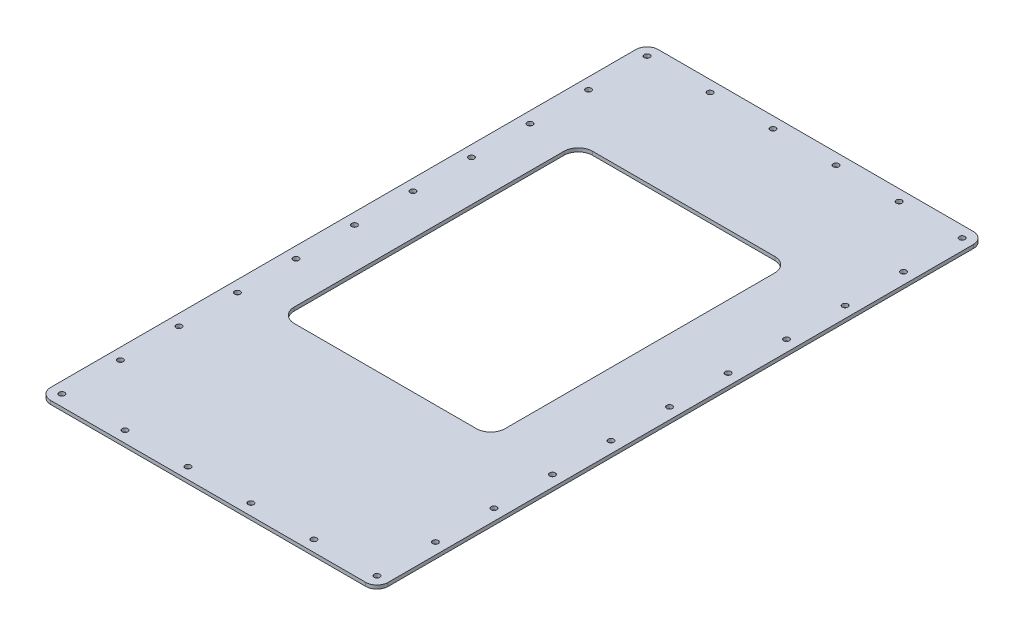
SolidWorks part; units mm, degrees
material "5052-H32"
ref_plane "Front Plane" through (0, 0, 0) normal (0, 0, 1) x (1, 0, 0)
ref_plane "Top Plane" through (0, 0, 0) normal (0, 1, 0) x (1, 0, 0)
ref_plane "Right Plane" through (0, 0, 0) normal (1, 0, 0) x (0, 0, -1)
sketch "Sketch9" plane through (0, 0, 0) normal (0, 1, 0) x (1, 0, 0)
  line L0 (-130, 0) -> (130, 0) construction
  line L1 (-130, 500) -> (130, 500) construction
  line L2 (-130, 500) -> (-130, 0) construction
  line L4 (130, 500) -> (130, 0) construction
  line L14 (83.6625, 147.4437) -> (-103.6625, 147.4437)
  line L15 (-150, 520) -> (150, 520)
  line L16 (150, 520) -> (150, -20)
  line L17 (-150, -20) -> (150, -20)
  line L18 (-150, 520) -> (-150, -20)
  line L19 (-10, 280) -> (155.5075, 280) construction
  line L20 (83.6625, 147.4437) -> (83.6625, 412.5562)
  line L21 (83.6625, 412.5562) -> (-103.6625, 412.5562)
  line L22 (-103.6625, 147.4437) -> (-103.6625, 412.5562)
  line L23 (83.6625, 147.4437) -> (-103.6625, 412.5562) construction
  line L24 (83.6625, 412.5562) -> (-103.6625, 147.4437) construction
  line L25 (-130, 0) -> (130, 0) construction
  point P5 (-10, 280)
  point P19 (0, 0)
  dimension "D10" = 500
  dimension "D9" = 260
  dimension "D3" = 265.1125
  dimension "D4" = 187.325
  dimension "D5" = 220
  dimension "D6" = 140
  dimension "D2" = 20
extrude "Boss-Extrude7" add sketch "Sketch9" along normal blind 3.175 separate body contours L15 L18 L17 L16 region at (0, 0, -513.8226)
fillet "Fillet4" radius 10 4 edges at (-150, 1.5875, -520) (150, 1.5875, -520) (-150, 1.5875, 20) (150, 1.5875, 20)
sketch "Sketch10" plane through (0, 0, 0) normal (0, 1, 0) x (1, 0, 0)
  line L0 (0, 0) -> (0, 500) construction
  line L1 (-130, 500) -> (130, 500) construction
  line L2 (-130, 500) -> (-130, 0) construction
  line L3 (-130, 0) -> (130, 0) construction
  line L4 (130, 500) -> (130, 0) construction
  line L8 (-150, 520) -> (-150, -20) construction
  line L9 (-150, -20) -> (150, -20) construction
  line L10 (150, 520) -> (150, -20) construction
  line L11 (-150, 520) -> (150, 520) construction
  line L15 (130, 250) -> (-130, 250) construction
  circle A0 centre (-140, -10) radius 2.5
  circle A2 centre (-140, 42) radius 2.5
  circle A3 centre (-140, 94) radius 2.5
  circle A4 centre (-140, 146) radius 2.5
  circle A5 centre (-140, 198) radius 2.5
  circle A6 centre (-140, 250) radius 2.5
  circle A7 centre (-140, 302) radius 2.5
  circle A8 centre (-140, 354) radius 2.5
  circle A9 centre (-140, 406) radius 2.5
  circle A10 centre (-140, 458) radius 2.5
  circle A16 centre (-140, 510) radius 2.5
  circle A17 centre (-84, 510) radius 2.5
  circle A18 centre (-28, 510) radius 2.5
  circle A19 centre (28, 510) radius 2.5
  circle A20 centre (84, 510) radius 2.5
  circle A21 centre (140, 510) radius 2.5
  circle A22 centre (140, 458) radius 2.5
  circle A23 centre (140, 406) radius 2.5
  circle A24 centre (140, 354) radius 2.5
  circle A25 centre (140, 302) radius 2.5
  circle A26 centre (140, 250) radius 2.5
  circle A27 centre (140, 198) radius 2.5
  circle A28 centre (140, 146) radius 2.5
  circle A29 centre (140, 94) radius 2.5
  circle A30 centre (140, 42) radius 2.5
  circle A31 centre (140, -10) radius 2.5
  circle A38 centre (84, -10) radius 2.5
  circle A39 centre (28, -10) radius 2.5
  circle A40 centre (-28, -10) radius 2.5
  circle A41 centre (-84, -10) radius 2.5
  dimension "D4" = 5
  dimension "D7" = 5
  dimension "D2" = 10
  dimension "D3" = 10
  dimension "D5" = 6
  dimension "D6" = 11
  dimension "D8" = 11
  dimension "D9" = 260
  dimension "D1" = 20
fillet "Fillet5" radius 12.7 4 edges at (-103.6625, 1.5875, -147.4437) (83.6625, 1.5875, -147.4437) (83.6625, 1.5875, -412.5562) (-103.6625, 1.5875, -412.5562)
extrude "Bolt Holes" cut sketch "Sketch10" along normal up to next (3.175 mm away)
equation "\"W\"= 260"
equation "\"D9@Sketch9\"=\"W\""
equation "\"L\"= 500"
equation "\"D10@Sketch9\"=\"L\""
equation "\"Offset\"= 20"
equation "\"D2@Sketch9\"=\"Offset\""
equation "\"D5@Sketch9\"=\"L\"/2-30"
equation "\"D6@Sketch9\"=\"W\"/2+10"
